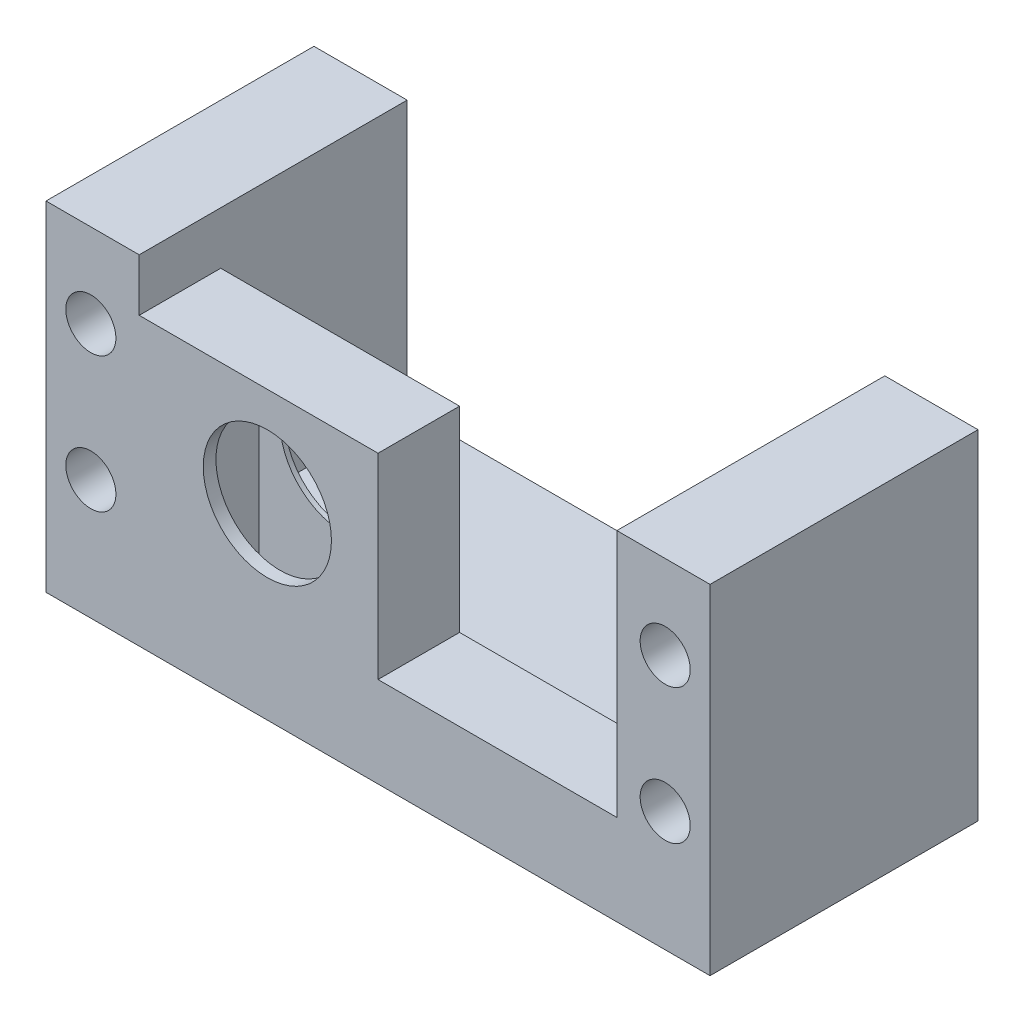
SolidWorks part; units mm, degrees
ref_plane "Спереди" through (0, 0, 0) normal (0, 0, 1) x (1, 0, 0)
ref_plane "Сверху" through (0, 0, 0) normal (0, 1, 0) x (1, 0, 0)
ref_plane "Справа" through (0, 0, 0) normal (1, 0, 0) x (0, 0, -1)
sketch "Эскиз1" plane through (0, 0, 0) normal (0, 0, 1) x (1, 0, 0)
  line L2 (-59.1906, -40.1769) -> (-59.1906, -15.0857)
  line L3 (-59.1906, -15.0857) -> (-51.1906, -15.0857)
  line L4 (-2.1906, -38.0857) -> (-2.1906, -15.0857)
  line L8 (-2.1906, -15.0857) -> (-10.1906, -15.0857)
  line L9 (-10.1906, -15.0857) -> (-10.1906, -38.0857)
  line L10 (-51.1906, -15.0857) -> (-51.1906, -38.0857)
  line L11 (-51.1906, -38.0857) -> (-10.1906, -38.0857)
  line L12 (-59.1906, -40.1769) -> (-59.1906, -44.1769)
  line L13 (-59.1906, -44.1769) -> (-2.1906, -44.1769)
  line L14 (-2.1906, -44.1769) -> (-2.1906, -38.0857)
  point P0 (0, 0)
extrude "Бобышка-Вытянуть1" add sketch "Эскиз1" along normal blind 23
sketch "Эскиз3" plane through (-59.1906, 0, 0) normal (-1, 0, 0) x (0, 0, 1)
  line L5 (0, -15.0857) -> (0, -44.1769) construction
  line L6 (15, -15.0857) -> (0, -15.0857) construction
  line L7 (15, -15.0857) -> (15, -38.2478) construction
  line L8 (15, -38.2478) -> (0, -38.2478) construction
  line L9 (0, -15.0857) -> (0, -38.2478) construction
sketch "Эскиз5" plane through (0, 0, 23) normal (0, 0, 1) x (1, 0, 0)
  line L0 (-51.1906, -38.0857) -> (-51.1906, -15.0857) construction
  line L1 (-10.1906, -28.0857) -> (-24.1906, -28.0857) construction
  line L6 (-30.6906, -18.0857) -> (-30.6906, -34.9839) construction
  line L11 (-51.1906, -28.0857) -> (-37.1906, -28.0857) construction
  line L12 (-10.1906, -38.0857) -> (-51.1906, -38.0857) construction
  line L13 (-10.1906, -38.0857) -> (-10.1906, -18.0857) construction
  line L14 (-10.1906, -18.0857) -> (-51.1906, -18.0857) construction
  line L15 (-51.1906, -38.0857) -> (-51.1906, -18.0857) construction
  line L16 (-21.1906, -34.9839) -> (-51.1906, -34.9839) construction
  line L18 (-21.1906, -19.5857) -> (-51.1906, -19.5857)
  line L19 (-51.1906, -34.9839) -> (-51.1906, -19.5857)
  line L20 (-21.1906, -19.5857) -> (-10.1906, -19.5857)
  line L22 (-21.1906, -34.9839) -> (-10.1906, -34.9839) construction
  line L23 (-10.1906, -19.5857) -> (-10.1906, -34.9839)
  line L24 (-10.1906, -38.0857) -> (-51.1906, -38.0857)
  line L25 (-51.1906, -38.0857) -> (-51.1906, -34.9839)
  line L26 (-10.1906, -38.0857) -> (-10.1906, -34.9839)
  circle A5 centre (-21.1906, -28.0857) radius 2.7
  circle A6 centre (-40.1906, -28.0857) radius 5.5
extrude "Бобышка-Вытянуть6" add sketch "Эскиз5" against normal blind 7
sketch "Эскиз6" plane through (0, 0, 23) normal (0, 0, 1) x (1, 0, 0)
  line L0 (-51.1906, -19.5857) -> (-51.1906, -15.0857) construction
  line L3 (-10.1906, -18.0857) -> (-51.1906, -18.0857)
  line L4 (-51.1906, -38.0857) -> (-51.1906, -18.0857)
  line L5 (-2.1906, -38.0857) -> (-59.1906, -38.0857) construction
  line L6 (-2.1906, -44.1769) -> (-2.1906, -15.0857) construction
  line L7 (-6.0406, -38.0857) -> (-6.0406, -29.5857) construction
  line L8 (-59.1906, -15.0857) -> (-59.1906, -44.1769) construction
  line L9 (-10.1906, -18.0857) -> (-2.1906, -18.0857) construction
  line L10 (-6.0406, -18.0857) -> (-6.0406, -26.5857) construction
  line L11 (-6.0406, -22.2857) -> (-10.1906, -22.2857) construction
  line L12 (-30.6906, -38.0857) -> (-30.6906, -18.0857) construction
  line L13 (-10.1906, -18.0857) -> (-10.1906, -38.0857) construction
  line L14 (-6.0406, -33.8857) -> (-10.1906, -33.8857) construction
  circle A1 centre (-6.0406, -33.8857) radius 2.15
  circle A3 centre (-6.0406, -22.2857) radius 2.15
  circle A4 centre (-55.3406, -22.2857) radius 2.15
  circle A5 centre (-55.3406, -33.8857) radius 2.15
extrude "Вырез-Вытянуть2" cut sketch "Эскиз6" against normal through all contours A1 | A3 | A5 | A4 region at (-6.0406, -33.8857, 23) region at (-6.0406, -22.2857, 23) region at (-55.3406, -22.2857, 23) region at (-55.3406, -33.8857, 23)
sketch "Эскиз8" plane through (0, 0, 23) normal (0, 0, 1) x (1, 0, 0)
  line L1 (-10.1906, -19.5857) -> (-30.6906, -19.5857)
  line L2 (-10.1906, -19.5857) -> (-10.1906, -36.4088)
  line L3 (-10.1906, -36.4088) -> (-30.6906, -36.4088)
  line L4 (-30.6906, -19.5857) -> (-30.6906, -36.4088)
extrude "Вырез-Вытянуть4" cut sketch "Эскиз8" against normal up to surface (7 mm away) up to face at (-45.6906, -28.0857, 16)
sketch "Эскиз16" plane through (0, 0, 23) normal (0, 0, 1) x (1, 0, 0)
  line L0 (-40.1906, -21.4357) -> (-40.1906, -34.7357)
  line L1 (-40.1906, -21.4357) -> (-43.9534, -21.4357) construction
  line L2 (-43.9534, -21.4357) -> (-43.9534, -44.1769) construction
  line L3 (-59.1906, -44.1769) -> (-2.1906, -44.1769) construction
  line L4 (-40.1906, -28.0857) -> (-40.1906, -44.1769) construction
  line L5 (-40.1906, -44.1769) -> (-39.0508, -41.093) construction
  point P4 (-40.1906, -28.0857)
sketch "Эскиз14" plane through (0, -44.1769, 0) normal (0, -1, 0) x (-1, 0, 0)
  line L0 (40.2278, -23) -> (40.2278, -19.1629) construction
  line L1 (59.1906, -23) -> (2.1906, -23) construction
  line L3 (32.9778, -21.9129) -> (47.4778, -21.9129)
  line L4 (32.9778, -21.9129) -> (32.9778, -16.4129)
  line L5 (32.9778, -16.4129) -> (47.4778, -16.4129)
  line L6 (47.4778, -21.9129) -> (47.4778, -16.4129)
  line L7 (32.9778, -21.9129) -> (47.4778, -16.4129) construction
  line L8 (32.9778, -16.4129) -> (47.4778, -21.9129) construction
extrude "Вырез-Вытянуть7" cut sketch "Эскиз14" against normal blind 22.74
